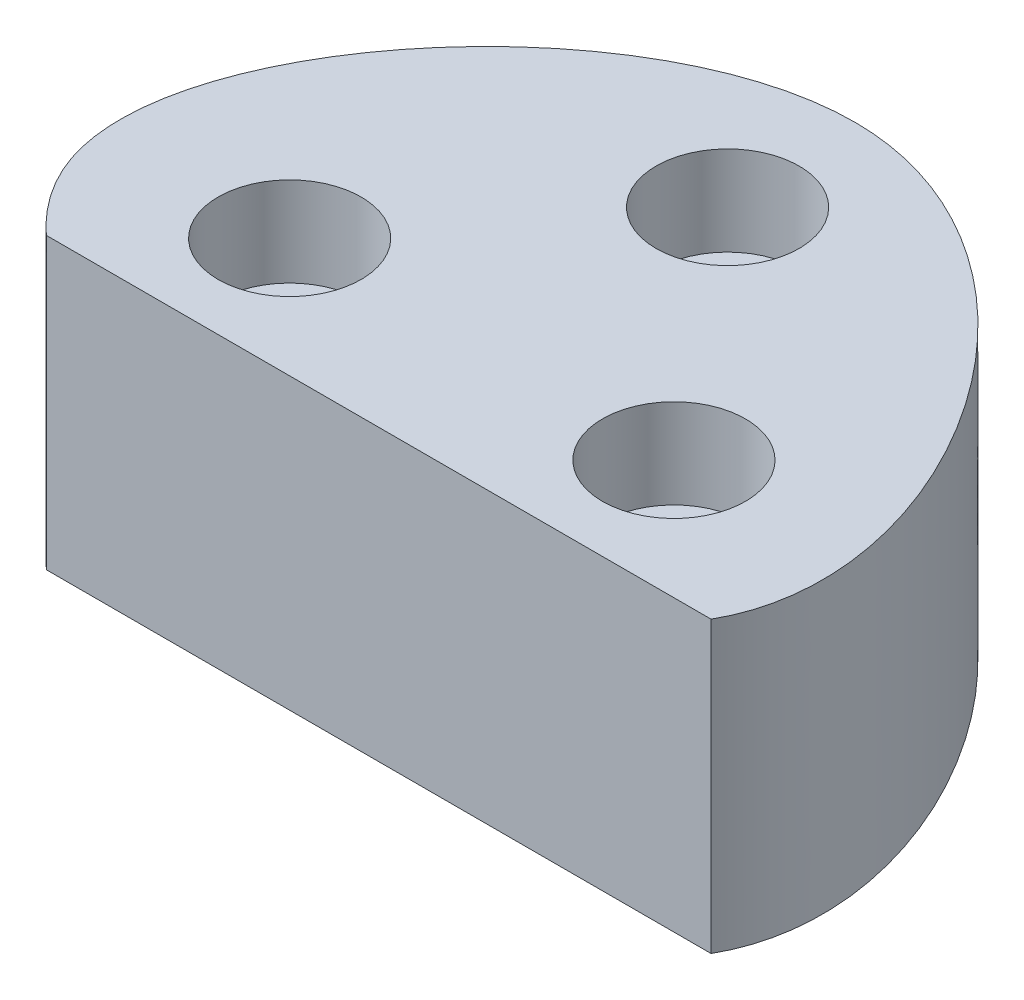
SolidWorks part; units mm, degrees
note: The reader was unsure of these and kept them because the rebuilt part matched: shared geometry of "Sketch10<5>".
ref_plane "Front Plane" through (0, 0, 0) normal (0, 0, 1) x (1, 0, 0)
ref_plane "Top Plane" through (0, 0, 0) normal (0, 1, 0) x (1, 0, 0)
ref_plane "Right Plane" through (0, 0, 0) normal (1, 0, 0) x (0, 0, -1)
sketch "Sketch2" plane through (0, 0, 0) normal (0, 1, 0) x (1, 0, 0)
  circle A0 centre (0, 0) radius 50
extrude "Boss-Extrude1" add sketch "Sketch2" along normal blind 16.2 contours A0
sketch "Sketch4" plane through (0, 16.2, 0) normal (0, 1, 0) x (1, 0, 0)
  circle A0 centre (0, 0) radius 4
  dimension "D1" = 8
sketch "Sketch7" plane through (0, 16.2, 0) normal (0, 1, 0) x (1, 0, 0)
  circle A0 centre (-10.75, -13.75) radius 4
  dimension "D1" = 8
extrude "Cut-Extrude2" cut sketch "Sketch7" against normal blind 5 contours A0
mirror "Mirror1" about plane through (0, 0, 0) normal (1, 0, 0) of "Cut-Extrude2"
extrude "Cut-Extrude3" cut sketch "Sketch4" against normal blind 5
sketch "Sketch10" plane through (0, 16.2, 0) normal (0, 1, 0) x (1, 0, 0)
  line L0 (-18.3895, -20.417) -> (19.4914, -20.417)
  line L1 (-18.3895, -20.417) -> (-18.3895, -33.817)
  line L2 (19.4914, -20.417) -> (19.4914, -33.817)
  line L3 (-18.3895, -33.817) -> (19.4914, -33.817)
  spline S0 degree 3 poles (38.7332, -33.4891) (1.6925, 24.281) (-39.7976, -25.754) (38.7332, -33.4891) (1.6925, 24.281) (-39.7976, -25.754) knots -1 -0.703327 -0.322215 0 0.296673 0.677785 1 1.296673 1.677785 2 only from (0, 7.6715) to (0, 7.6715)
  circle M4 centre (0, 0) radius 50
extrude "Cut-Extrude6" cut sketch "Sketch10" against normal blind 20 contours L0 S0 | S0 L0 L1 L3 L2 | S0 L2 L3 L1 L0 M4
extrude "Cut-Extrude7" cut sketch "Sketch10<5>" against normal blind 20 contours L0 S0 | S0 L0 L1 L3 L2
sketch "Sketch10<5>" plane through (0, 16.2, 0) normal (0, 1, 0) x (1, 0, 0) same geometry as "Sketch10"
